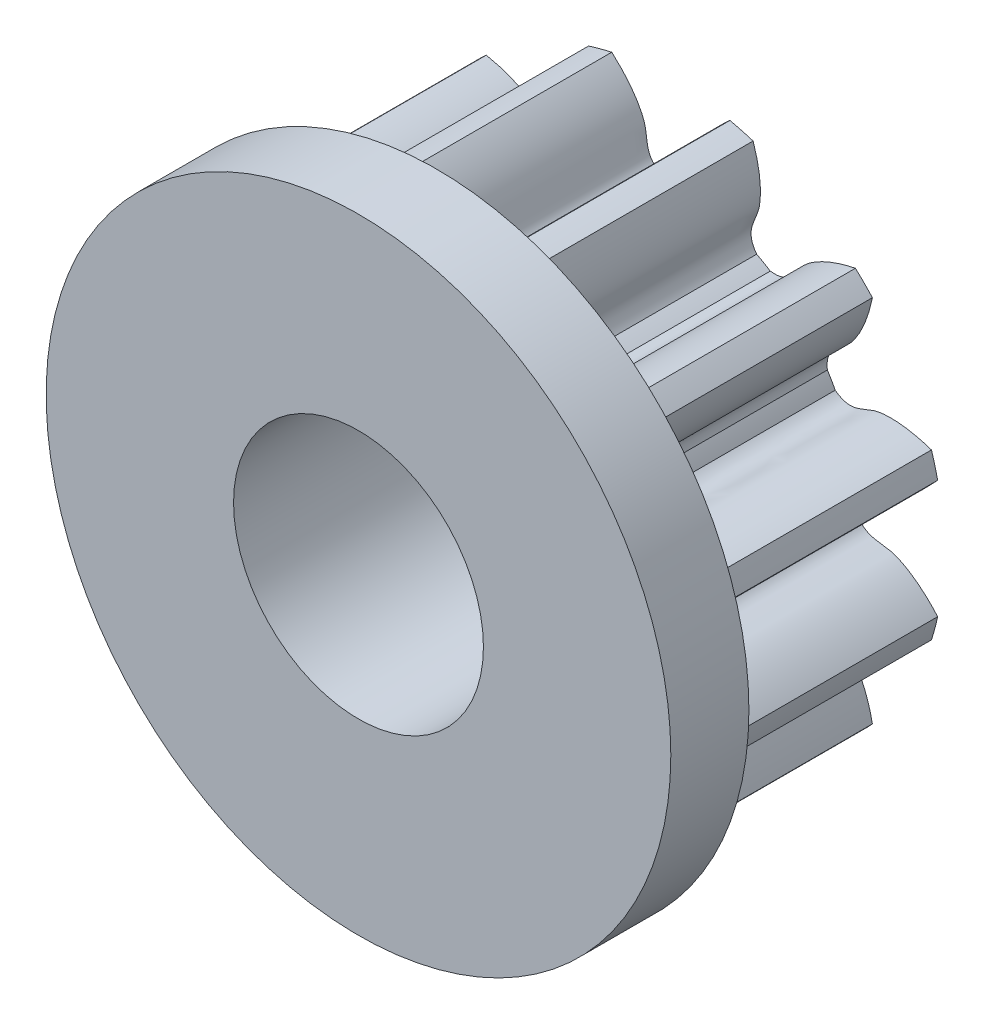
SolidWorks part; units mm, degrees
ref_plane "前视基准面" through (0, 0, 0) normal (0, 0, 1) x (1, 0, 0)
ref_plane "上视基准面" through (0, 0, 0) normal (0, 1, 0) x (1, 0, 0)
ref_plane "右视基准面" through (0, 0, 0) normal (1, 0, 0) x (0, 0, -1)
other "Configuration Table"
sketch "草图1" plane through (0, 0, 0) normal (0, 0, 1) x (1, 0, 0)
  circle A0 centre (0, 0) radius 3.5
extrude "凸台-拉伸1" add sketch "草图1" along normal blind 3
ref_axis "基准轴1" through (0, 0, 3) along (0, 0, -1)
sketch "草图2" plane through (0, 0, 0) normal (0, 0, 1) x (1, 0, 0)
  line L0 (0, 0) -> (0, 3.5) construction
  circle A0 centre (0, 0) radius 3.5 construction
  arc A1 (0.1004, 2.3729) -> (-0.1004, 2.3729) centre (0, 0) ccw
  arc A2 (1.7488, 3.9475) -> (-1.7488, 3.9475) centre (0, 0) ccw
  spline S0 degree 3 poles (0.1004, 2.3729) (0.3404, 2.4747) (0.2872, 2.6724) (0.3381, 2.8447) (0.3413, 2.855) (0.3451, 2.8662) (0.3495, 2.8784) (0.3546, 2.8915) (0.3603, 2.9056) (0.3668, 2.9206) (0.374, 2.9366) (0.3821, 2.9533) (0.3909, 2.971) (0.4007, 2.9894) (0.4114, 3.0086) (0.423, 3.0286) (0.4356, 3.0493) (0.4492, 3.0707) (0.4639, 3.0928) (0.4796, 3.1155) (0.4965, 3.1388) (0.5145, 3.1626) (0.5337, 3.187) (0.554, 3.2119) (0.5756, 3.2372) (0.5985, 3.2629) (0.6226, 3.289) (0.648, 3.3154) (0.6748, 3.342) (0.7028, 3.369) (0.7323, 3.3961) (0.7631, 3.4234) (0.7954, 3.4507) (0.829, 3.4782) (0.8641, 3.5057) (0.9006, 3.5331) (0.9385, 3.5604) (0.978, 3.5877) (1.0189, 3.6147) (1.0613, 3.6416) (1.1052, 3.6681) (1.1506, 3.6944) (1.1975, 3.7203) (1.2459, 3.7457) (1.2958, 3.7707) (1.3472, 3.7952) (1.4001, 3.8191) (1.4546, 3.8424) (1.5105, 3.865) (1.5679, 3.8869) (1.6472, 3.9154) (1.7078, 3.9351) (1.7488, 3.9475) knots 0 0 0 0 0.218015 0.222044 0.226546 0.231522 0.236972 0.242897 0.249295 0.256167 0.263513 0.271332 0.279626 0.288394 0.297636 0.307351 0.317541 0.328204 0.339341 0.350953 0.363038 0.375597 0.38863 0.402137 0.416118 0.430573 0.445502 0.460904 0.476781 0.493132 0.509956 0.527255 0.545027 0.563273 0.581994 0.601188 0.620856 0.640998 0.661614 0.682704 0.704268 0.726305 0.748817 0.771803 0.795262 0.819196 0.843603 0.868484 0.89384 0.919669 0.945972 1 1 1 1
  spline S1 degree 3 poles (-0.1004, 2.3729) (-0.3404, 2.4747) (-0.2872, 2.6724) (-0.3381, 2.8447) (-0.3413, 2.855) (-0.3451, 2.8662) (-0.3495, 2.8784) (-0.3546, 2.8915) (-0.3603, 2.9056) (-0.3668, 2.9206) (-0.374, 2.9366) (-0.3821, 2.9533) (-0.3909, 2.971) (-0.4007, 2.9894) (-0.4114, 3.0086) (-0.423, 3.0286) (-0.4356, 3.0493) (-0.4492, 3.0707) (-0.4639, 3.0928) (-0.4796, 3.1155) (-0.4965, 3.1388) (-0.5145, 3.1626) (-0.5337, 3.187) (-0.554, 3.2119) (-0.5756, 3.2372) (-0.5985, 3.2629) (-0.6226, 3.289) (-0.648, 3.3154) (-0.6748, 3.342) (-0.7028, 3.369) (-0.7323, 3.3961) (-0.7631, 3.4234) (-0.7954, 3.4507) (-0.829, 3.4782) (-0.8641, 3.5057) (-0.9006, 3.5331) (-0.9385, 3.5604) (-0.978, 3.5877) (-1.0189, 3.6147) (-1.0613, 3.6416) (-1.1052, 3.6681) (-1.1506, 3.6944) (-1.1975, 3.7203) (-1.2459, 3.7457) (-1.2958, 3.7707) (-1.3472, 3.7952) (-1.4001, 3.8191) (-1.4546, 3.8424) (-1.5105, 3.865) (-1.5679, 3.8869) (-1.6472, 3.9154) (-1.7078, 3.9351) (-1.7488, 3.9475) knots 0 0 0 0 0.218015 0.222044 0.226546 0.231522 0.236972 0.242897 0.249295 0.256167 0.263513 0.271332 0.279626 0.288394 0.297636 0.307351 0.317541 0.328204 0.339341 0.350953 0.363038 0.375597 0.38863 0.402137 0.416118 0.430573 0.445502 0.460904 0.476781 0.493132 0.509956 0.527255 0.545027 0.563273 0.581994 0.601188 0.620856 0.640998 0.661614 0.682704 0.704268 0.726305 0.748817 0.771803 0.795262 0.819196 0.843603 0.868484 0.89384 0.919669 0.945972 1 1 1 1
extrude "切除-拉伸1" cut sketch "草图2" along normal through all
pattern_circular "阵列(圆周)1" count 12 every 30 about axis through (0, 0, 3) along (0, 0, -1) of "切除-拉伸1"
sketch "草图3" plane through (0, 0, 0) normal (0, 0, 1) x (1, 0, 0)
  circle A0 centre (0, 0) radius 3 construction
  dimension "Dn" = 6
sketch "草图5" plane through (0, 0, 3) normal (0, 0, 1) x (1, 0, 0)
  circle A0 centre (0, 0) radius 4 construction
  circle A1 centre (0, 0) radius 4
extrude "凸台-拉伸2" add sketch "草图5" along normal blind 1
sketch "草图6" plane through (0, 0, 4) normal (0, 0, 1) x (1, 0, 0)
  circle A0 centre (0, 0) radius 1.6 construction
  circle A1 centre (0, 0) radius 1.6
extrude "切除-拉伸2" cut sketch "草图6" against normal blind 10
